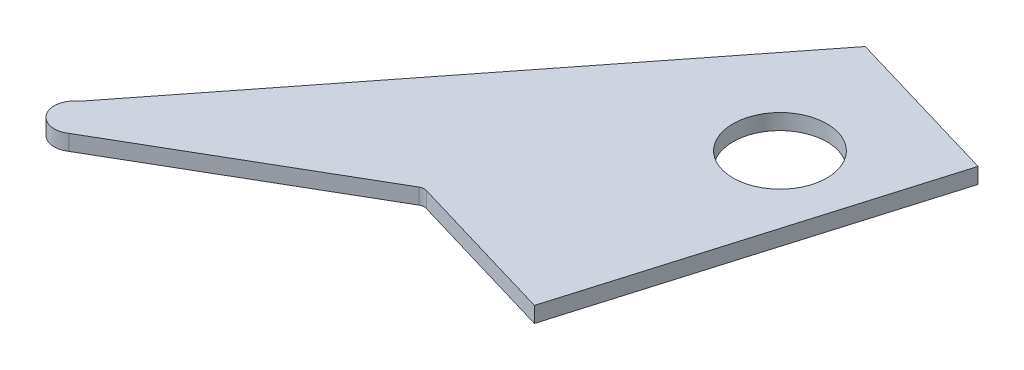
SolidWorks part; units mm, degrees
ref_plane "Front Plane" through (0, 0, 0) normal (0, 0, 1) x (1, 0, 0)
ref_plane "Top Plane" through (0, 0, 0) normal (0, 1, 0) x (1, 0, 0)
ref_plane "Right Plane" through (0, 0, 0) normal (1, 0, 0) x (0, 0, -1)
sketch "Sketch1" plane through (0, 0, 0) normal (0, 1, 0) x (1, 0, 0)
  line L0 (53.8544, 73.3734) -> (102.5625, 58.9454)
  line L1 (22.9946, -31.525) -> (-44.3261, -70.5626)
  line L2 (-51.2626, -60.5757) -> (53.8544, 73.3734)
  line L4 (102.5625, 58.9454) -> (71.7331, -45.1328)
  line L5 (71.7331, -45.1328) -> (24.9902, -31.2869)
  arc A0 (-44.3261, -70.5626) -> (-51.2626, -60.5757) centre (-47.7944, -65.5691) cw
  arc A2 (22.9946, -31.525) -> (24.9902, -31.2869) centre (24.2688, -33.7223) cw
  dimension "D1" = 2.54
extrude "Boss-Extrude1" add sketch "Sketch1" along normal blind 4.7625
sketch "Sketch2" plane through (0, 4.7625, 0) normal (0, 1, 0) x (1, 0, 0)
  circle A0 centre (68.3614, 32.9161) radius 14.2875
  point P3 (68.3614, 32.9161)
extrude "Cut-Extrude1" cut sketch "Sketch2" against normal through all
